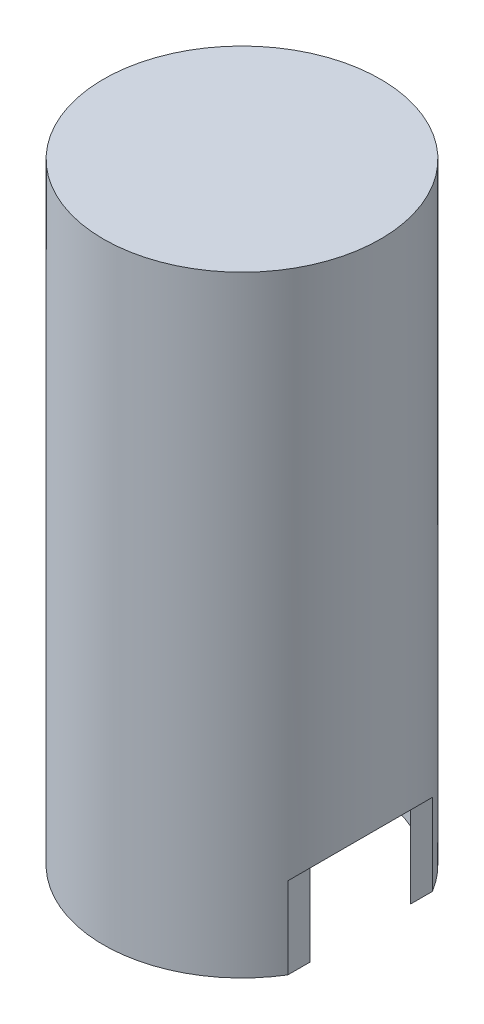
SolidWorks part; units mm, degrees
ref_plane "Front Plane" through (0, 0, 0) normal (0, 0, 1) x (1, 0, 0)
ref_plane "Top Plane" through (0, 0, 0) normal (0, 1, 0) x (1, 0, 0)
ref_plane "Right Plane" through (0, 0, 0) normal (1, 0, 0) x (0, 0, -1)
sketch "Sketch3" plane through (0, 0, 0) normal (0, 1, 0) x (1, 0, 0)
  circle A0 centre (0, 0) radius 68
  dimension "D1" = 136
extrude "Boss-Extrude1" add sketch "Sketch3" along normal blind 300
ref_axis "Axis1" through (0, 300, 0) along (0, -1, 0)
shell "Shell1" thickness 5 removed face at (0, 0, 68)
sketch "Sketch8" plane through (0, 0, 0) normal (0, 0, 1) x (1, 0, 0)
  line L0 (-68, 0) -> (-58, 0)
  line L1 (-68, 0) -> (68, 0) construction
  line L2 (-58, 0) -> (-58, 40)
  line L4 (-68, 300) -> (-68, 0) construction
  line L5 (-68, 50) -> (-68, 0)
  line L6 (-58, 40) -> (-68, 50)
  line L7 (0, -74.8) -> (0, 74.8) construction
  line L8 (68, 0) -> (58, 0)
  line L9 (58, 0) -> (58, 40)
  line L10 (58, 40) -> (68, 50)
  line L11 (68, 50) -> (68, 0)
  dimension "D1" = 10
  dimension "D2" = 50
  dimension "D3" = 40
extrude "Cut-Extrude3" cut sketch "Sketch8" against normal through all both and the other way through all
